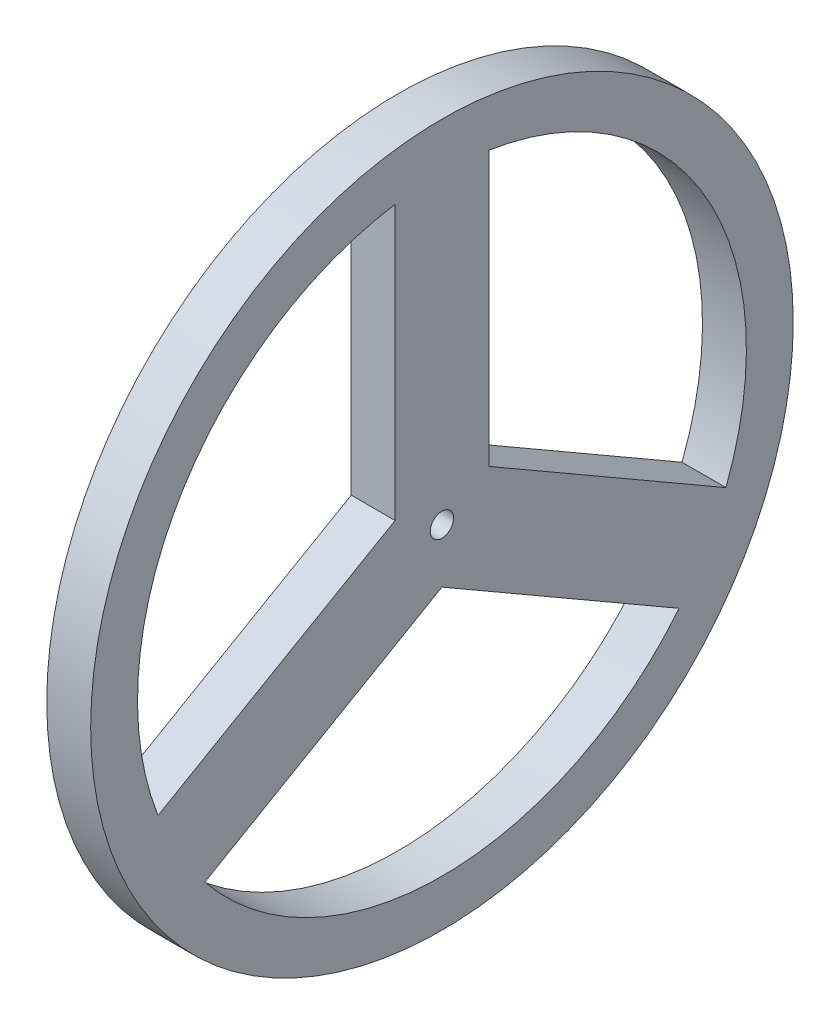
SolidWorks part; units mm, degrees
material "Corrugated Paper"
ref_plane "Front Plane" through (0, 0, 0) normal (0, 0, 1) x (1, 0, 0)
ref_plane "Top Plane" through (0, 0, 0) normal (0, 1, 0) x (1, 0, 0)
ref_plane "Right Plane" through (0, 0, 0) normal (1, 0, 0) x (0, 0, -1)
sketch "Sketch2" plane through (0, 0, 0) normal (1, 0, 0) x (0, 0, -1)
  line L0 (0, 33.02) -> (0, 0) construction
  line L1 (0, 0) -> (28.5962, -16.51) construction
  line L2 (0, 0) -> (-28.5962, -16.51) construction
  line L3 (-2.54, -4.3994) -> (26.0562, -20.9094)
  line L4 (-2.54, 4.3994) -> (-31.1362, -12.1106)
  line L5 (-5.08, 33.02) -> (-5.08, 0)
  line L6 (2.54, 4.3994) -> (31.1362, -12.1106)
  line L7 (2.54, -4.3994) -> (-26.0562, -20.9094)
  line L8 (5.08, 33.02) -> (5.08, 0)
  circle A0 centre (0, 0) radius 38.1
  circle A1 centre (0, 0) radius 33.02
  circle A2 centre (0, 0) radius 5.08
  circle A3 centre (0, 0) radius 1.27
  dimension "D1" = 76.2
  dimension "D3" = 10.16
  dimension "D4" = 2.54
  dimension "D5" = 120
  dimension "D6" = 120
  dimension "D2" = 5.08
  dimension "D7" = 5.08
  dimension "D8" = 5.08
extrude "Boss-Extrude5" add sketch "Sketch2" along normal blind 4.7625 contours A0
extrude "Cut-Extrude3" cut sketch "Sketch2<3>" along direction (1, 0, 0) on the side of the normal through all contours L7 A1 L3 | L5 A1 L4 | L6 A1 L8 | A3 region at (0, -21.1007, 0) region at (0, 10.5503, 18.2737) region at (0, 10.5503, -18.2737) region at (0, 0, 0)
sketch "Sketch2<3>" plane through (0, 0, 0) normal (1, 0, 0) x (0, 0, -1) same geometry as "Sketch2"
equation "\"rodThick\"= 0.1in"
equation "\"thick\"= 3 / 16"
equation "\"D1@Boss-Extrude5\"=\"thick\""
equation "\"D4@Sketch2\"=\"rodThick\""
